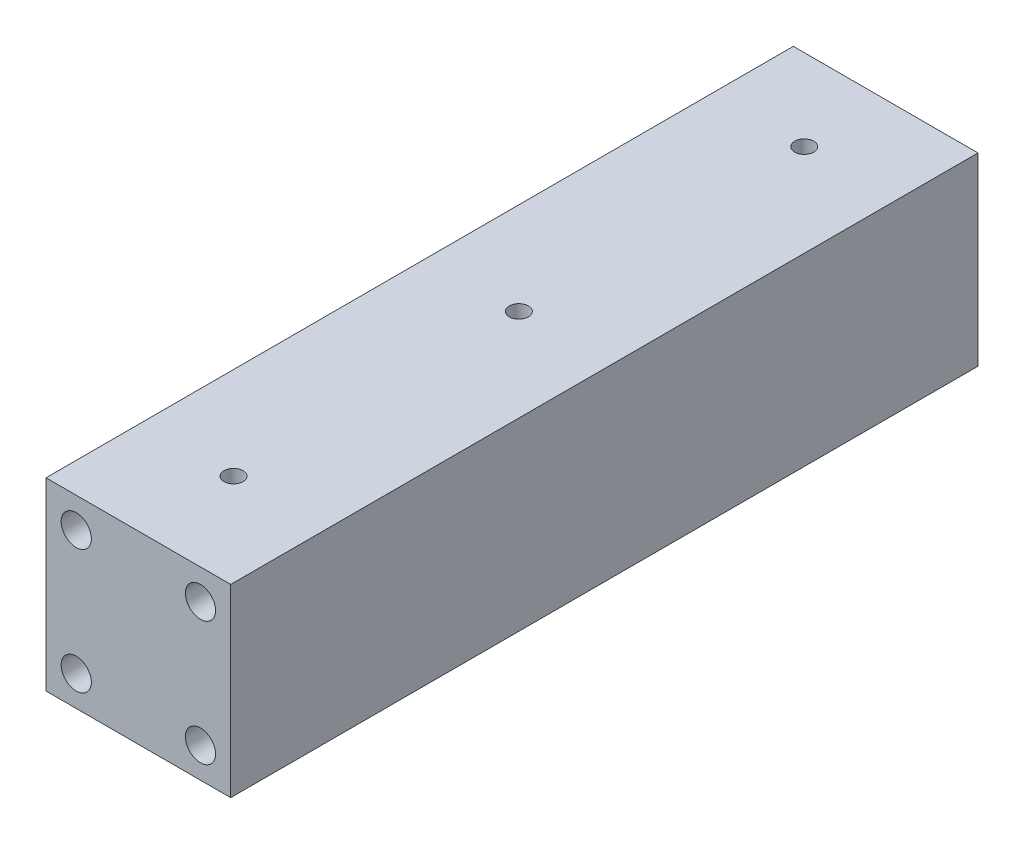
SolidWorks part; units mm, degrees
ref_plane "Front Plane" through (0, 0, 0) normal (0, 0, 1) x (1, 0, 0)
ref_plane "Top Plane" through (0, 0, 0) normal (0, 1, 0) x (1, 0, 0)
ref_plane "Right Plane" through (0, 0, 0) normal (1, 0, 0) x (0, 0, -1)
sketch "Sketch1" plane through (0, 0, 0) normal (0, 1, 0) x (1, 0, 0)
  line L0 (-12.9005, 156.9999) -> (25.9005, 156.9999)
  line L1 (-12.9005, 156.9999) -> (-12.9005, 0)
  line L2 (-12.9005, 0) -> (25.9005, 0)
  line L3 (25.9005, 0) -> (25.9005, 156.9999)
  point P6 (6.5, 156.9999)
  line B0 (0, 0) -> (13, 0)
  line B1 (13, 0) -> (13, 156.9999)
  line B2 (13, 156.9999) -> (0, 156.9999)
  line B3 (0, 156.9999) -> (0, 0)
  circle B4 centre (6.5, 139.888) radius 2
  circle B5 centre (6.5, 79.944) radius 2
  circle B6 centre (6.5, 20) radius 2
  dimension "D1" = 38.801
sketch_block_instance "Block-ForwardDirSliderBaseMounting-1"
sketch_block "Block-ForwardDirSliderBaseMounting"
extrude "Boss-Extrude1" add sketch "Sketch1" along normal blind 38.801 contours B3 L0 L1 L2 | L0 B3 L2 B1 B6 B5 B4 | B1 L2 L3 L0 | B6 | B4 | B5 region at (-6.4503, 0, -78.5) region at (6.5, 0, -155.4246) region at (19.4503, 0, -78.5) region at (6.5, 0, -139.888) region at (6.5, 0, -79.944) region at (6.5, 0, -20)
extrude "Cut-Extrude1" cut sketch "Sketch1<3>" against normal blind 6.35 from surface contours B6 | B5 | B4 region at (6.5, 0, -139.888) region at (6.5, 0, -79.944) region at (6.5, 0, -20) starting at face at (6.5, 38.801, -78.5)
sketch "Sketch1<3>" plane through (0, 0, 0) normal (0, 1, 0) x (1, 0, 0) same geometry as "Sketch1"
sketch "Sketch2" plane through (0, 0, 0) normal (0, 0, 1) x (1, 0, 0)
  line B0 (-12.9005, 38.801) -> (25.9005, 0) construction
  line B1 (-12.9005, 0) -> (25.9005, 38.801) construction
  line B2 (-12.9005, 0) -> (25.9005, 0)
  line B3 (25.9005, 0) -> (25.9005, 38.801)
  line B4 (25.9005, 38.801) -> (-12.9005, 38.801)
  line B5 (-12.9005, 38.801) -> (-12.9005, 0)
  circle B6 centre (19.5505, 32.451) radius 3.175
  arc B7 (7.934, 87.7816) -> (4.9621, 78.7327) centre (6.5, 83.2401) ccw
  circle B8 centre (-6.5505, 32.451) radius 3.175
  circle B9 centre (-6.5505, 6.35) radius 3.175
  circle B10 centre (19.5505, 6.35) radius 3.175
  spline B11 degree 3 poles (4.9621, 78.7327) (4.9637, 78.768) (4.9886, 78.7984) (5.0483, 78.8359) (5.0821, 78.8472) (5.1834, 78.874) (5.2525, 78.8823) (5.4605, 78.9027) (5.6002, 78.9085) (6.0182, 78.9323) (6.2965, 78.954) (7.1252, 79.0838) (7.6495, 79.2567) (8.6327, 79.7915) (9.0633, 80.1373) (9.6077, 80.7761) (9.7661, 81.0027) (10.0375, 81.4829) (10.1509, 81.7393) (10.325, 82.2687) (10.3854, 82.5384) (10.4545, 83.0878) (10.4627, 83.37) (10.4259, 83.9231) (10.3815, 84.1959) (10.2405, 84.7337) (10.1433, 84.9979) (9.7836, 85.7456) (9.4519, 86.2027) (8.8703, 86.8029) (8.6613, 86.9893) (8.3414, 87.2598) (8.2331, 87.3481) (8.0783, 87.4892) (8.0275, 87.5373) (7.9622, 87.6192) (7.942, 87.6481) (7.9164, 87.7134) (7.9144, 87.7524) (7.934, 87.7816) knots 0 0 0 0 0.007812 0.007812 0.015625 0.015625 0.03125 0.03125 0.0625 0.0625 0.125 0.125 0.25 0.25 0.375 0.375 0.4375 0.4375 0.5 0.5 0.5625 0.5625 0.625 0.625 0.6875 0.6875 0.75 0.75 0.875 0.875 0.9375 0.9375 0.96875 0.96875 0.984375 0.984375 0.992188 0.992188 1 1 1 1
sketch_block_instance "Block-ForwardMotorPlate-1"
sketch_block "Block-ForwardMotorPlate" parameters "D2"=6.35, "D1"=6.35
extrude "Cut-Extrude2" cut sketch "Sketch2" against normal blind 12.7 contours B8 | B6 | B10 | B9 region at (19.5505, 32.451, 0) region at (-6.5505, 32.451, 0) region at (-6.5505, 6.35, 0) region at (19.5505, 6.35, 0)
extrude "Cut-Extrude3" cut sketch "Sketch2<3>" along normal blind 12.7 from surface contours B8 | B6 | B10 | B9 region at (19.5505, 32.451, 0) region at (-6.5505, 32.451, 0) region at (-6.5505, 6.35, 0) region at (19.5505, 6.35, 0) starting at face at (6.5, 19.4005, -156.9999)
sketch "Sketch2<3>" plane through (0, 0, 0) normal (0, 0, 1) x (1, 0, 0) same geometry as "Sketch2"
